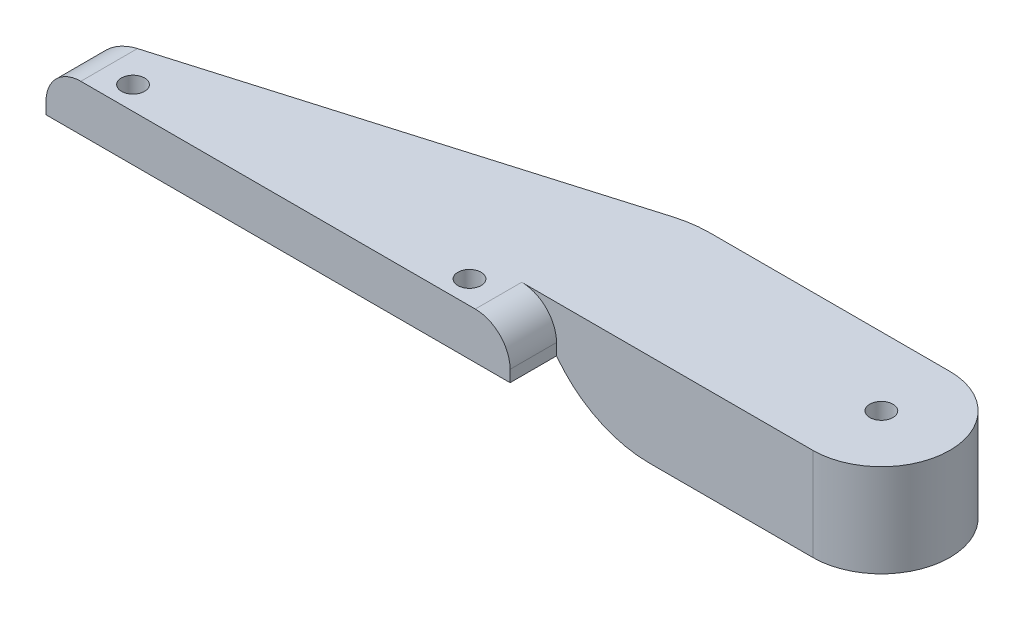
SolidWorks part; units mm, degrees
ref_plane "Front Plane" through (0, 0, 0) normal (0, 0, 1) x (1, 0, 0)
ref_plane "Top Plane" through (0, 0, 0) normal (0, 1, 0) x (1, 0, 0)
ref_plane "Right Plane" through (0, 0, 0) normal (1, 0, 0) x (0, 0, -1)
sketch "Sketch1" plane through (0, 0, 0) normal (0, 1, 0) x (1, 0, 0)
  line L0 (-20, 2) -> (20, 13.8)
  line L1 (-20, -2) -> (20, -2)
  line L2 (-20, -2) -> (-20, 2)
  line L3 (-20, 2) -> (20, 2) construction
  line L4 (20, -2) -> (20, 2)
  line L5 (-20, -2) -> (20, 2) construction
  line L6 (-20, 2) -> (20, -2) construction
  line L7 (20, 13.8) -> (20, 2) construction
  line L8 (20, 7.9) -> (48, 7.9) construction
  line L11 (20, 13.8) -> (42.1, 13.8)
  line L12 (42.1, 13.8) -> (42.1, 2) construction
  line L13 (20, 2) -> (42.1, 2)
  arc A2 (42.1, 13.8) -> (42.1, 2) centre (42.1, 7.9) cw
  point P0 (0, 0)
extrude "Boss-Extrude2" add sketch "Sketch1" along normal blind 4
ref_plane "Plane1" through (0, -4, 0) normal (0, -1, 0) x (-1, 0, 0)
sketch "Sketch2" plane through (0, 0, 0) normal (0, 1, 0) x (1, 0, 0)
  line L0 (42.1, 13.8) -> (42.1, 2) construction
  line L5 (26.1497, 7.9) -> (45.7842, 7.9) construction
  line L6 (42.1, 18.1892) -> (42.1, -2.3892) construction
  line L7 (27.9813, 9.8929) -> (39.8678, 10.8763) construction
  line L8 (27.9813, 5.9071) -> (39.8997, 4.9) construction
  circle A9 centre (42.1, 7.9) radius 3.6842 construction
  arc A16 (27.9813, 9.8929) -> (27.9813, 5.9071) centre (28.1497, 7.9) ccw construction
  arc A17 (39.8678, 10.8763) -> (39.8997, 4.9) centre (42.1, 7.9) ccw construction
  point P0 (53.3853, 10.5001)
  point P3 (46.1609, 22.3448)
  point P5 (49.6378, 19.3514)
  point P29 (51.9992, 11.3401)
  point P37 (42.1, 7.9)
ref_plane "Plane2" through (0, 0, 0) normal (0, -1, 0) x (-1, 0, 0)
sketch "Sketch4" plane through (0, 0, 0) normal (0, -1, 0) x (-1, 0, 0)
  line L1 (-20, 2) -> (-42.1, 2)
  line L2 (-20, 2) -> (-20, 13.8)
  line L3 (-20, 13.8) -> (-42.1, 13.8)
  line L4 (-42.1, 2) -> (-42.1, 13.8) construction
  arc A0 (-42.1, 2) -> (-42.1, 13.8) centre (-42.1, 7.9) cw
extrude "Boss-Extrude3" add sketch "Sketch4" along normal blind 4
ref_plane "Plane3" through (0, -4, 0) normal (0, -1, 0) x (-1, 0, 0)
sketch "Sketch6" plane through (0, -4, 0) normal (0, -1, 0) x (1, 0, 0)
  line L0 (39.8997, -4.9) -> (27.9813, -5.9071)
  line L1 (27.9813, -5.9071) -> (39.8997, -4.9) construction
  line L2 (27.9813, -9.8929) -> (39.8678, -10.8763)
  line L3 (42.1, -2) -> (42.1, -13.8) construction
  line L4 (42.1, -7.9) -> (26.1497, -7.9) construction
  line L5 (27.9813, -9.8929) -> (27.9813, -5.9071) construction
  circle A0 centre (42.1, -7.9) radius 3.6842 construction
  arc A1 (27.9813, -5.9071) -> (27.9813, -9.8929) centre (27.9813, -7.9) ccw
  arc A2 (27.9813, -5.9071) -> (27.9813, -9.8929) centre (28.1497, -7.9) ccw construction
  arc A3 (39.8997, -4.9) -> (39.8678, -10.8763) centre (42.1, -7.9) cw
extrude "Cut-Extrude1" cut sketch "Sketch6" against normal blind 4
sketch "Sketch7" plane through (0, 0, 0) normal (0, -1, 0) x (1, 0, 0)
  circle A0 centre (42.1, -7.9) radius 1
extrude "Cut-Extrude2" cut sketch "Sketch7" against normal through all
sketch "Sketch9" plane through (0, 4, 0) normal (0, 1, 0) x (1, 0, 0)
  line L0 (-20, 0) -> (-14.5, 0) construction
  line L1 (-20, 2) -> (-20, -2) construction
  line L2 (20, 0) -> (14.5, 0) construction
  line L3 (20, -2) -> (20, 2) construction
  circle A0 centre (-14.5, 0) radius 1
  circle A1 centre (14.5, 0) radius 1
extrude "Cut-Extrude8" cut sketch "Sketch9" against normal through all
fillet "Fillet1" radius 10 1 edges at (20, -4, -7.9)
fillet "Fillet2" radius 10 1 edges at (20, 2, -13.8)
fillet "Fillet3" radius 3 2 edges at (-20, 4, 0) (20, 4, 0)
